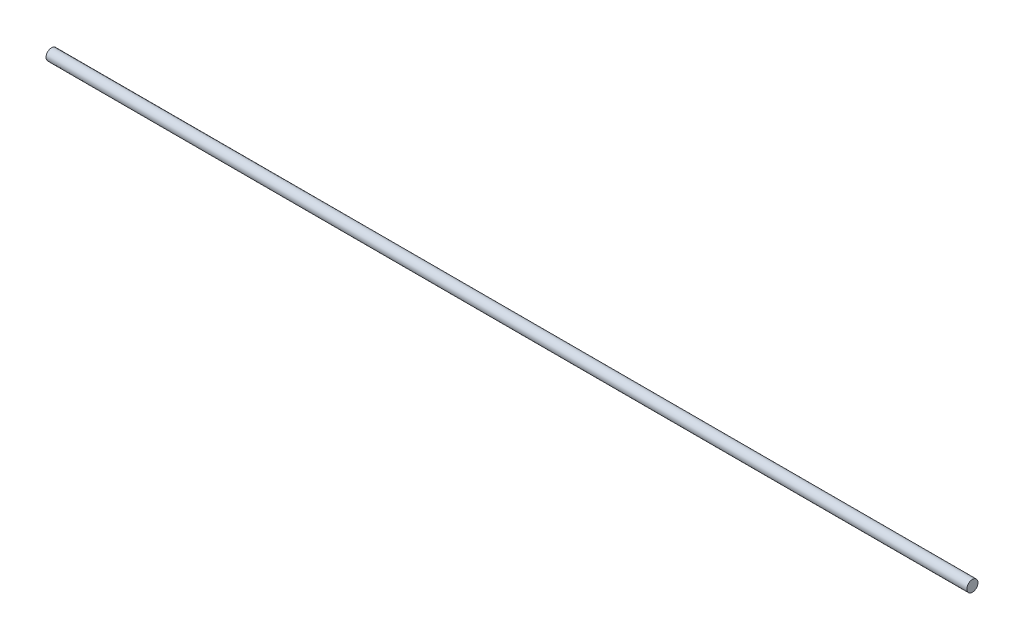
SolidWorks part; units mm, degrees
ref_plane "Front Plane" through (0, 0, 0) normal (0, 0, 1) x (1, 0, 0)
ref_plane "Top Plane" through (0, 0, 0) normal (0, 1, 0) x (1, 0, 0)
ref_plane "Right Plane" through (0, 0, 0) normal (1, 0, 0) x (0, 0, -1)
sketch "Sketch1" plane through (0, 0, 0) normal (1, 0, 0) x (0, 0, -1)
  circle A0 centre (0, 0) radius 1
  dimension "D1" = 2
extrude "Boss-Extrude1" add sketch "Sketch1" along normal blind 82.5 and the other way blind 82.5
